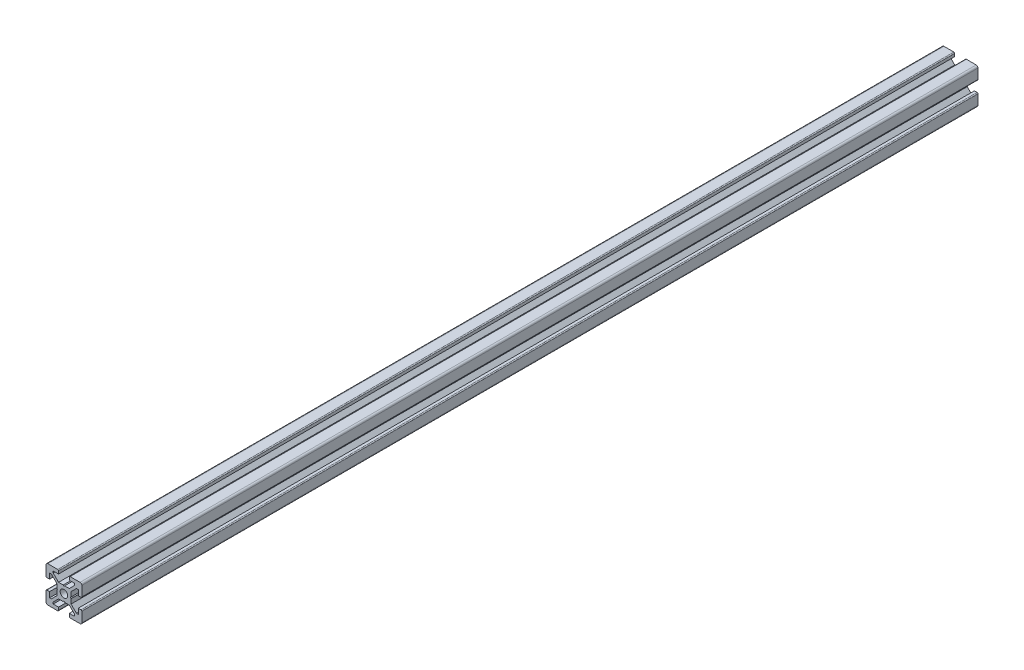
SolidWorks part; units mm, degrees
material "Lega 6061"
ref_plane "Piano frontale" through (0, 0, 0) normal (0, 0, 1) x (1, 0, 0)
ref_plane "Piano superiore" through (0, 0, 0) normal (0, 1, 0) x (1, 0, 0)
ref_plane "Piano destro" through (0, 0, 0) normal (1, 0, 0) x (0, 0, -1)
sketch "Schizzo1" plane through (0, 0, 0) normal (0, 0, 1) x (1, 0, 0)
  line L0 (0, 0) -> (-10, 0) construction
  line L1 (0, 0) -> (0, 10) construction
  line L2 (-3.6, 0) -> (-4, 0.4)
  line L3 (-4, 0.4) -> (-4, 3)
  line L4 (-4, 3) -> (-7, 6)
  line L5 (-7, 6) -> (-8, 6)
  line L6 (-8, 6) -> (-8, 3)
  line L7 (-8, 3) -> (-9.5, 3)
  line L8 (-10, 3.5) -> (-10, 9)
  line L9 (0, 0) -> (-10, 10) construction
  line L10 (0, 3.6) -> (-0.4, 4)
  line L11 (-0.4, 4) -> (-3, 4)
  line L12 (-3, 4) -> (-6, 7)
  line L13 (-6, 7) -> (-6, 8)
  line L14 (-6, 8) -> (-3, 8)
  line L15 (-3, 8) -> (-3, 9.5)
  line L16 (-3.5, 10) -> (-9, 10)
  line L17 (0, 0) -> (-10, -10) construction
  line L18 (-3.5, -10) -> (-9, -10)
  line L19 (-3, -8) -> (-3, -9.5)
  line L20 (-6, -8) -> (-3, -8)
  line L21 (-6, -7) -> (-6, -8)
  line L22 (-3, -4) -> (-6, -7)
  line L23 (-0.4, -4) -> (-3, -4)
  line L24 (0, -3.6) -> (-0.4, -4)
  line L25 (-10, -3.5) -> (-10, -9)
  line L26 (-8, -3) -> (-9.5, -3)
  line L27 (-8, -6) -> (-8, -3)
  line L28 (-7, -6) -> (-8, -6)
  line L29 (-4, -3) -> (-7, -6)
  line L30 (-4, -0.4) -> (-4, -3)
  line L31 (-3.6, 0) -> (-4, -0.4)
  line L32 (0, 0) -> (10, -10) construction
  line L33 (0, 0) -> (10, 10) construction
  line L34 (3.6, 0) -> (4, -0.4)
  line L35 (4, -0.4) -> (4, -3)
  line L36 (4, -3) -> (7, -6)
  line L37 (7, -6) -> (8, -6)
  line L38 (8, -6) -> (8, -3)
  line L39 (8, -3) -> (9.5, -3)
  line L40 (10, -3.5) -> (10, -9)
  line L41 (0, -3.6) -> (0.4, -4)
  line L42 (0.4, -4) -> (3, -4)
  line L43 (3, -4) -> (6, -7)
  line L44 (6, -7) -> (6, -8)
  line L45 (6, -8) -> (3, -8)
  line L46 (3, -8) -> (3, -9.5)
  line L47 (3.5, -10) -> (9, -10)
  line L48 (3.5, 10) -> (9, 10)
  line L49 (3, 8) -> (3, 9.5)
  line L50 (6, 8) -> (3, 8)
  line L51 (6, 7) -> (6, 8)
  line L52 (3, 4) -> (6, 7)
  line L53 (0.4, 4) -> (3, 4)
  line L54 (0, 3.6) -> (0.4, 4)
  line L55 (10, 3.5) -> (10, 9)
  line L56 (8, 3) -> (9.5, 3)
  line L57 (8, 6) -> (8, 3)
  line L58 (7, 6) -> (8, 6)
  line L59 (4, 3) -> (7, 6)
  line L60 (4, 0.4) -> (4, 3)
  line L61 (3.6, 0) -> (4, 0.4)
  arc A0 (-10, 9) -> (-9, 10) centre (-9, 9) cw
  arc A1 (-3, 9.5) -> (-3.5, 10) centre (-3.5, 9.5) ccw
  arc A2 (-9.5, 3) -> (-10, 3.5) centre (-9.5, 3.5) cw
  arc A3 (-9.5, -3) -> (-10, -3.5) centre (-9.5, -3.5) ccw
  arc A4 (-3, -9.5) -> (-3.5, -10) centre (-3.5, -9.5) cw
  arc A5 (-10, -9) -> (-9, -10) centre (-9, -9) ccw
  arc A6 (10, -9) -> (9, -10) centre (9, -9) cw
  arc A7 (3, -9.5) -> (3.5, -10) centre (3.5, -9.5) ccw
  arc A8 (9.5, -3) -> (10, -3.5) centre (9.5, -3.5) cw
  arc A9 (9.5, 3) -> (10, 3.5) centre (9.5, 3.5) ccw
  arc A10 (3, 9.5) -> (3.5, 10) centre (3.5, 9.5) cw
  arc A11 (10, 9) -> (9, 10) centre (9, 9) ccw
  circle A12 centre (0, 0) radius 2.1
  point P24 (-3, 10)
  point P27 (-10, 3)
  point P49 (-10, -3)
  point P50 (-3, -10)
  point P92 (3, -10)
  point P93 (10, -3)
  point P94 (10, 3)
  point P95 (3, 10)
  dimension "D2" = 1
  dimension "D12" = 0.5
  dimension "D13" = 4.2
  dimension "D3" = 8
  dimension "D4" = 0.4
  dimension "D5" = 45
  dimension "D6" = 6
  dimension "D7" = 12
  dimension "D8" = 20
  dimension "D9" = 2
  dimension "D10" = 4
  dimension "D11" = 45
extrude "Estrusione-Estrusione1" add sketch "Schizzo1" along normal blind 500
sketch "Schizzo2" plane through (-10, 0, 0) normal (-1, 0, 0) x (0, 0, 1)
  line L0 (500, 0) -> (0, 0) construction
  line L1 (0, -3.5) -> (0, -9) construction
  line L2 (250, 0.4) -> (250, 18.0033) construction
  line L3 (500, 0.4) -> (0, 0.4) construction
  circle A0 centre (25, 0) radius 3
  circle A1 centre (475, 0) radius 3
  dimension "D2" = 6
  dimension "D1" = 25
extrude "Taglio-Estrusione5" cut sketch "Schizzo2" against normal through all both and the other way through all
